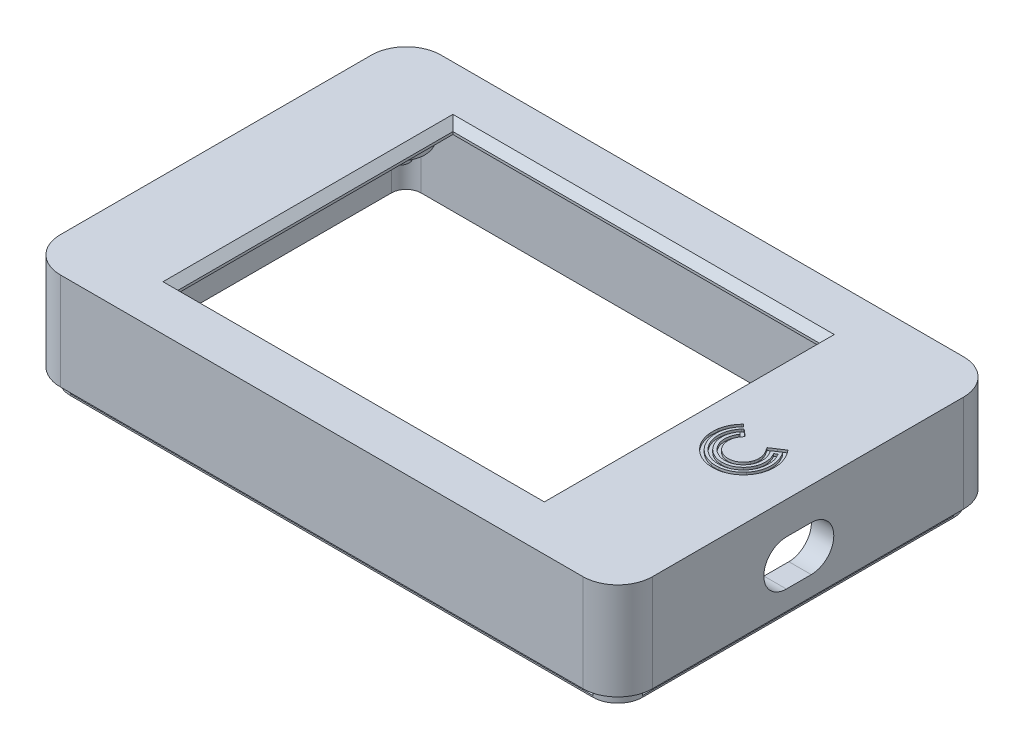
SolidWorks part; units mm, degrees
note: The reader was unsure of these and kept them because the rebuilt part matched: shared geometry of "Esquisse32<2>", "Esquisse48<2>".
other "Marquage2"
sketch "Esquisse44" plane through (-47.6, -20, 30.6) normal (-0.0394, -0.9945, 0.0967) x (-0.9946, 0.0483, 0.0914)
ref_plane "Front Plane" through (0, 0, 0) normal (0, 0, 1) x (1, 0, 0)
ref_plane "Top Plane" through (0, 0, 0) normal (0, 1, 0) x (1, 0, 0)
ref_plane "Right Plane" through (0, 0, 0) normal (1, 0, 0) x (0, 0, -1)
sketch "Esquisse1" plane through (0, 0, 0) normal (0, 1, 0) x (1, 0, 0)
  line L1 (-46, 29) -> (46, 29)
  line L2 (-46, 29) -> (-46, -29)
  line L3 (-46, -29) -> (46, -29)
  line L4 (46, 29) -> (46, -29)
  line L5 (-46, 29) -> (46, -29) construction
  line L6 (-46, -29) -> (46, 29) construction
  line L7 (-43, 25) -> (43, 25) construction
  line L8 (-43, 25) -> (-43, -25) construction
  line L9 (-31.6, -22.1) -> (27.3, -22.1)
  line L10 (-31.6, -22.1) -> (-31.6, 22.1)
  line L11 (-31.6, 22.1) -> (27.3, 22.1)
  line L12 (27.3, -22.1) -> (27.3, 22.1)
  line L13 (-31.6, -22.1) -> (27.3, 22.1) construction
  line L14 (-31.6, 22.1) -> (27.3, -22.1) construction
  line L15 (-43, -25) -> (43, -25) construction
  line L16 (43, 25) -> (43, -25) construction
  line L17 (-43, 25) -> (43, -25) construction
  line L18 (-43, -25) -> (43, 25) construction
  point P0 (0, 0)
  point P6 (0, 0)
  point P9 (-2.15, 0)
  dimension "D1" = 58
  dimension "D2" = 92
  dimension "D3" = 50
  dimension "D4" = 44.2
  dimension "D5" = 58.9
  dimension "D6" = 86
  dimension "D7" = 15.7
  dimension "D8" = 11.4
extrude "Boss.-Extru.1" add sketch "Esquisse1" along normal blind 1.6
fillet "Congé1" radius 4 4 edges at (46, 0.8, 29) (46, 0.8, -29) (-46, 0.8, 29) (-46, 0.8, -29)
chamfer "Chanfrein1" distance 1.2 angle 45 4 edges at (-2.15, 1.6, -22.1) (-31.6, 1.6, 0) (-2.15, 1.6, 22.1) (27.3, 1.6, 0)
sketch "Esquisse12" plane through (0, 0, 0) normal (0, -1, 0) x (1, 0, 0)
  line L0 (0, 0) -> (-39, 0) construction
  line L1 (-39, 21) -> (39, 21) construction
  line L2 (-39, 21) -> (-39, -21) construction
  line L3 (-39, -21) -> (39, -21) construction
  line L4 (39, 21) -> (39, -21) construction
  line L5 (-39, 21) -> (39, -21) construction
  line L6 (-39, -21) -> (39, 21) construction
  line L7 (-39, 0) -> (-45.8499, 0) construction
  circle A0 centre (-39, 21) radius 4
  circle A1 centre (-39, -21) radius 4
  circle A2 centre (39, 21) radius 4
  circle A3 centre (39, -21) radius 4
  point P0 (0, 0)
  dimension "D1" = 42
  dimension "D2" = 78
extrude "Boss.-Extru.2" add sketch "Esquisse12" along normal blind 4 contours A1 | A0 | A3 | A2
sketch "Esquisse13" plane through (0, 0, 0) normal (0, -1, 0) x (1, 0, 0)
  circle A1 centre (-39, 21) radius 1.45
  circle A2 centre (-39, -21) radius 1.45
  circle A3 centre (39, -21) radius 1.45
  circle A4 centre (39, 21) radius 1.45
extrude "Boss.-Extru.3" add sketch "Esquisse13" along normal blind 6.4
sketch "Esquisse32" plane through (0, 0, 0) normal (0, -1, 0) x (1, 0, 0)
  line L4 (46, -25) -> (46, 25)
  line L6 (46, -25) -> (46, 25)
  line L12 (42, 29) -> (-42, 29)
  line L14 (42, 29) -> (-42, 29)
  line L16 (-46, 25) -> (-46, -25)
  line L17 (-46, 25) -> (-46, -25)
  line L18 (-42, -29) -> (42, -29)
  line L19 (-42, -29) -> (42, -29)
  arc A4 (46, 25) -> (42, 29) centre (42, 25) ccw
  arc A6 (46, 25) -> (42, 29) centre (42, 25) ccw
  arc A12 (-42, 29) -> (-46, 25) centre (-42, 25) ccw
  arc A14 (-42, 29) -> (-46, 25) centre (-42, 25) ccw
  arc A16 (-46, -25) -> (-42, -29) centre (-42, -25) ccw
  arc A17 (-46, -25) -> (-42, -29) centre (-42, -25) ccw
  arc A18 (42, -29) -> (46, -25) centre (42, -25) ccw
  arc A19 (42, -29) -> (46, -25) centre (42, -25) ccw
  dimension "D1" = 0
extrude "Extru.-Mince3" add sketch "Esquisse32" along normal blind 16 thin thin type one direction reverse wall 1.6
extrude "Extru.-Mince4" add sketch "Esquisse32<2>" along normal blind 14 and the other way blind 1.6 thin
sketch "Esquisse32<2>" plane through (0, 0, 0) normal (0, -1, 0) x (1, 0, 0) same geometry as "Esquisse32"
sketch3d "Esquisse3D2"
  line L0 (-46, -14, -25) -> (-46, -16, -25) construction
  line L6 (-46, -15, -25) -> (-46, -15.75, -25)
  line L7 (-46, -15, -25) -> (-46, -14.25, -25)
  line L8 (-46, -14.25, -25) -> (-45.25, -15, -25)
  line L9 (-45.25, -15, -25) -> (-46, -15.75, -25)
extrude "Enlèv. mat.-Extru.3 ok" cut sketch "Esquisse3D2" along direction (0, 0, -1) on the side of the normal blind 50
sketch3d "Esquisse3D3"
  line L0 (46, -16, -25) -> (46, -14, -25) construction
  line L5 (46, -15, -25) -> (46, -15.75, -25)
  line L6 (46, -15, -25) -> (46, -14.25, -25)
  line L7 (46, -15.75, -25) -> (45.25, -15, -25)
  line L8 (45.25, -15, -25) -> (46, -14.25, -25)
extrude "Enlèv. mat.-Extru.4 ok" cut sketch "Esquisse3D3" along direction (0, 0, 1) on the side against the normal blind 50
sketch3d "Esquisse3D4"
  line L0 (42, -16, 29) -> (42, -14, 29) construction
  line L1 (42, -16, 27.4) -> (42, 0, 27.4) construction
  line L2 (42, -15, 29) -> (42, -14.25, 29)
  line L4 (42, -15, 29) -> (42, -14.25, 29)
  line L5 (42, -15, 29) -> (42, -15.75, 29)
  line L8 (42, -15.75, 29) -> (42, -15, 28.25)
  line L9 (42, -15, 28.25) -> (42, -14.25, 29)
extrude "Enlèv. mat.-Extru.5" cut sketch "Esquisse3D4" along direction (-1, 0, 0) on the side of the normal blind 84 contours L4 L5 L8 L9
sketch "Esquisse45" plane through (0, 1.6, 0) normal (0, 1, 0) x (1, 0, 0)
  line L2 (47.6, 0) -> (28.5, 0) construction
  line L3 (38.05, 0) -> (37.55, 0) construction
  line L4 (47.6, 25) -> (47.6, -25) construction
  line L6 (28.5, 23.3) -> (28.5, -23.3) construction
  point P0 (37.2387, 0)
  line B0 (34.2158, 2.7113) -> (34.3885, 2.9127)
  line B1 (34.3885, 2.9127) -> (34.4378, 2.8723)
  spline B2 degree 3 poles (32.2337, -0.3842) (32.2377, -0.4186) (32.2519, -0.5344) (32.264, -0.6416) knots 0 0 0 0 1 1 1 1
  spline B3 degree 3 poles (32.264, -0.6416) (32.3608, -1.4972) (32.7507, -2.4235) (33.303, -3.113) knots 1 1 1 1 2 2 2 2
  spline B4 degree 3 poles (33.303, -3.113) (33.4921, -3.3501) (33.8794, -3.7342) (34.1159, -3.9223) knots 2 2 2 2 3 3 3 3
  spline B5 degree 3 poles (34.1159, -3.9223) (34.8233, -4.4844) (35.7228, -4.8635) (36.5984, -4.9704) knots 3 3 3 3 4 4 4 4
  spline B6 degree 3 poles (36.5984, -4.9704) (36.9003, -5.0068) (37.7725, -4.9915) (38.0171, -4.946) knots 4 4 4 4 5 5 5 5
  spline B7 degree 3 poles (38.0171, -4.946) (38.532, -4.8532) (38.9035, -4.7337) (39.3593, -4.5183) knots 5 5 5 5 6 6 6 6
  spline B8 degree 3 poles (39.3593, -4.5183) (40.5052, -3.9735) (41.3817, -3.0412) (41.8615, -1.851) knots 6 6 6 6 7 7 7 7
  spline B9 degree 3 poles (41.8615, -1.851) (41.9771, -1.5647) (42.0958, -1.1348) (42.1539, -0.7967) knots 7 7 7 7 8 8 8 8
  spline B10 degree 3 poles (42.1539, -0.7967) (42.2119, -0.4607) (42.2156, 0.3707) (42.1644, 0.7032) knots 8 8 8 8 9 9 9 9
  spline B11 degree 3 poles (42.1644, 0.7032) (42.0391, 1.4819) (41.7529, 2.2231) (41.3225, 2.8733) knots 9 9 9 9 10 10 10 10
  spline B12 degree 3 poles (41.3225, 2.8733) (41.1105, 3.194) (40.8811, 3.4892) (40.8532, 3.4722) knots 10 10 10 10 11 11 11 11
  spline B13 degree 3 poles (40.8532, 3.4722) (40.8403, 3.4638) (40.3817, 3.1649) (39.835, 2.8066) knots 11 11 11 11 12 12 12 12
  spline B14 degree 3 poles (39.835, 2.8066) (39.5035, 2.5889) (39.1719, 2.3712) (38.8404, 2.1536) knots 12 12 12 12 13 13 13 13
  spline B15 degree 3 poles (38.8404, 2.1536) (38.9054, 2.0538) (38.9705, 1.9541) (39.0355, 1.8544) knots 13 13 13 13 14 14 14 14
  spline B16 degree 3 poles (39.0355, 1.8544) (39.381, 1.3248) (39.5374, 1.0087) (39.6375, 0.6245) knots 14 14 14 14 15 15 15 15
  spline B17 degree 3 poles (39.6375, 0.6245) (39.6876, 0.4377) (39.6916, 0.3863) (39.6888, -0.008) knots 15 15 15 15 16 16 16 16
  spline B18 degree 3 poles (39.6888, -0.008) (39.686, -0.4044) (39.6814, -0.4515) (39.6265, -0.6482) knots 16 16 16 16 17 17 17 17
  spline B19 degree 3 poles (39.6265, -0.6482) (39.5935, -0.7637) (39.5149, -0.9667) (39.4519, -1.097) knots 17 17 17 17 18 18 18 18
  spline B20 degree 3 poles (39.4519, -1.097) (38.7411, -2.5405) (36.904, -2.9519) (35.6554, -1.9446) knots 18 18 18 18 19 19 19 19
  spline B21 degree 3 poles (35.6554, -1.9446) (35.2612, -1.6269) (34.9623, -1.1748) (34.8242, -0.6895) knots 19 19 19 19 20 20 20 20
  spline B22 degree 3 poles (34.8242, -0.6895) (34.7448, -0.404) (34.7207, -0.1831) (34.7379, 0.1317) knots 20 20 20 20 21 21 21 21
  spline B23 degree 3 poles (34.7379, 0.1317) (34.7723, 0.7572) (34.9859, 1.2742) (35.407, 1.747) knots 21 21 21 21 22 22 22 22
  spline B24 degree 3 poles (35.407, 1.747) (35.5388, 1.8917) (35.5583, 1.9259) (35.5349, 1.9475) knots 22 22 22 22 23 23 23 23
  spline B25 degree 3 poles (35.5349, 1.9475) (35.5178, 1.9647) (35.275, 2.1679) (34.9938, 2.4034) knots 23 23 23 23 24 24 24 24
  spline B26 degree 3 poles (34.9938, 2.4034) (34.7126, 2.6389) (34.4634, 2.8485) (34.4378, 2.8723) knots 24 24 24 24 25 25 25 25
  spline B27 degree 3 poles (34.2158, 2.7113) (32.6545, 0.8902) (32.8979, -1.7703) (34.7563, -3.2073) knots 26 26 26 26 27 27 27 27
  spline B28 degree 3 poles (34.7563, -3.2073) (36.3328, -4.4248) (38.5491, -4.3067) (40.0012, -2.9264) knots 27 27 27 27 28 28 28 28
  spline B29 degree 3 poles (40.0012, -2.9264) (40.4497, -2.4988) (40.8092, -1.9419) (41.0188, -1.3519) knots 28 28 28 28 29 29 29 29
  spline B30 degree 3 poles (41.0188, -1.3519) (41.1937, -0.8539) (41.2521, -0.4579) (41.239, 0.1186) knots 29 29 29 29 30 30 30 30
  spline B31 degree 3 poles (41.239, 0.1186) (41.2292, 0.5623) (41.1819, 0.854) (41.056, 1.2448) knots 30 30 30 30 31 31 31 31
  spline B32 degree 3 poles (41.056, 1.2448) (40.9847, 1.4682) (40.687, 2.0981) (40.6463, 2.1112) knots 31 31 31 31 32 32 32 32
  spline B33 degree 3 poles (40.6463, 2.1112) (40.6292, 2.1177) (40.2679, 1.9015) (40.2119, 1.8525) knots 32 32 32 32 33 33 33 33
  spline B34 degree 3 poles (40.2119, 1.8525) (40.2075, 1.8483) (40.2561, 1.7451) (40.3216, 1.6225) knots 33 33 33 33 34 34 34 34
  spline B35 degree 3 poles (40.3216, 1.6225) (40.7763, 0.7558) (40.8507, -0.2454) (40.5271, -1.1667) knots 34 34 34 34 35 35 35 35
  spline B36 degree 3 poles (40.5271, -1.1667) (40.35, -1.669) (40.0748, -2.0977) (39.6735, -2.4956) knots 35 35 35 35 36 36 36 36
  spline B37 degree 3 poles (39.6735, -2.4956) (38.9507, -3.2105) (38.0762, -3.5515) (37.0737, -3.5081) knots 36 36 36 36 37 37 37 37
  spline B38 degree 3 poles (37.0737, -3.5081) (36.5274, -3.4849) (36.1168, -3.3771) (35.6406, -3.138) knots 37 37 37 37 38 38 38 38
  spline B39 degree 3 poles (35.6406, -3.138) (35.2904, -2.962) (35.0261, -2.7673) (34.7218, -2.4587) knots 38 38 38 38 39 39 39 39
  spline B40 degree 3 poles (34.7218, -2.4587) (34.0559, -1.7855) (33.7125, -0.941) (33.7192, 0.0125) knots 39 39 39 39 40 40 40 40
  spline B41 degree 3 poles (33.7192, 0.0125) (33.7229, 0.5374) (33.8181, 0.9696) (34.0337, 1.4609) knots 40 40 40 40 41 41 41 41
  spline B42 degree 3 poles (34.0337, 1.4609) (34.1186, 1.6532) (34.3181, 1.9946) (34.4089, 2.1054) knots 41 41 41 41 42 42 42 42
  spline B43 degree 3 poles (34.4089, 2.1054) (34.4262, 2.126) (34.4435, 2.1466) (34.4607, 2.1672) knots 42 42 42 42 43 43 43 43
  spline B44 degree 3 poles (34.4607, 2.1672) (34.5182, 2.1182) (34.5758, 2.0692) (34.6333, 2.0202) knots 43 43 43 43 44 44 44 44
  spline B45 degree 3 poles (34.6333, 2.0202) (34.7291, 1.9403) (34.8079, 1.8712) (34.8079, 1.8669) knots 44 44 44 44 45 45 45 45
  spline B46 degree 3 poles (34.8079, 1.8669) (34.8079, 1.8647) (34.7559, 1.7815) (34.6909, 1.6813) knots 45 45 45 45 46 46 46 46
  spline B47 degree 3 poles (34.6909, 1.6813) (34.2099, 0.9261) (34.0743, -0.0736) (34.3406, -0.9133) knots 46 46 46 46 47 47 47 47
  spline B48 degree 3 poles (34.3406, -0.9133) (34.5293, -1.5039) (34.9239, -2.0616) (35.4206, -2.4315) knots 47 47 47 47 48 48 48 48
  spline B49 degree 3 poles (35.4206, -2.4315) (35.6422, -2.5981) (36.0928, -2.8241) (36.3494, -2.8987) knots 48 48 48 48 49 49 49 49
  spline B50 degree 3 poles (36.3494, -2.8987) (36.6894, -2.9975) (36.912, -3.0269) (37.2914, -3.0167) knots 49 49 49 49 50 50 50 50
  spline B51 degree 3 poles (37.2914, -3.0167) (37.4821, -3.0117) (37.7051, -2.9918) (37.7952, -2.9731) knots 50 50 50 50 51 51 51 51
  spline B52 degree 3 poles (37.7952, -2.9731) (39.0034, -2.7181) (39.9053, -1.8244) (40.1731, -0.6157) knots 51 51 51 51 52 52 52 52
  spline B53 degree 3 poles (40.1731, -0.6157) (40.2351, -0.329) (40.2456, 0.2495) (40.1899, 0.552) knots 52 52 52 52 53 53 53 53
  spline B54 degree 3 poles (40.1899, 0.552) (40.1218, 0.9382) (39.9576, 1.3529) (39.6971, 1.7919) knots 53 53 53 53 54 54 54 54
  spline B55 degree 3 poles (39.6971, 1.7919) (39.6548, 1.8636) (39.6124, 1.9353) (39.5701, 2.007) knots 54 54 54 54 55 55 55 55
  spline B56 degree 3 poles (39.5701, 2.007) (39.7631, 2.1321) (39.9561, 2.2572) (40.1491, 2.3822) knots 55 55 55 55 56 56 56 56
  spline B57 degree 3 poles (40.1491, 2.3822) (40.4677, 2.59) (40.7389, 2.7595) (40.7496, 2.7594) knots 56 56 56 56 57 57 57 57
  spline B58 degree 3 poles (40.7496, 2.7594) (40.8053, 2.759) (41.1673, 2.1265) (41.3211, 1.759) knots 57 57 57 57 58 58 58 58
  spline B59 degree 3 poles (41.3211, 1.759) (41.9934, 0.1601) (41.724, -1.6015) (40.6048, -2.92) knots 58 58 58 58 59 59 59 59
  spline B60 degree 3 poles (40.6048, -2.92) (39.8853, -3.7699) (38.855, -4.3155) (37.7206, -4.4511) knots 59 59 59 59 60 60 60 60
  spline B61 degree 3 poles (37.7206, -4.4511) (37.3796, -4.4937) (36.8054, -4.479) (36.478, -4.421) knots 60 60 60 60 61 61 61 61
  spline B62 degree 3 poles (36.478, -4.421) (34.417, -4.0615) (32.8905, -2.3602) (32.7594, -0.2765) knots 61 61 61 61 62 62 62 62
  spline B63 degree 3 poles (32.7594, -0.2765) (32.6804, 0.984) (33.1131, 2.183) (33.9677, 3.0599) knots 62 62 62 62 63 63 63 63
  spline B64 degree 3 poles (33.9677, 3.0599) (34.0044, 3.0975) (34.0411, 3.1351) (34.0778, 3.1727) knots 63 63 63 63 64 64 64 64
  spline B65 degree 3 poles (34.0778, 3.1727) (34.0523, 3.1957) (34.0267, 3.2187) (34.0012, 3.2418) knots 64 64 64 64 65 65 65 65
  spline B66 degree 3 poles (34.0012, 3.2418) (33.9564, 3.2806) (33.867, 3.3584) (33.801, 3.4189) knots 65 65 65 65 66 66 66 66
  spline B67 degree 3 poles (33.801, 3.4189) (33.7598, 3.4549) (33.7186, 3.4909) (33.6775, 3.5269) knots 66 66 66 66 67 67 67 67
  spline B68 degree 3 poles (33.6775, 3.5269) (33.6321, 3.4772) (33.5868, 3.4275) (33.5414, 3.3778) knots 67 67 67 67 68 68 68 68
  spline B69 degree 3 poles (33.5414, 3.3778) (32.8635, 2.6476) (32.4439, 1.7913) (32.2827, 0.8025) knots 68 68 68 68 69 69 69 69
  spline B70 degree 3 poles (32.2827, 0.8025) (32.2491, 0.5927) (32.2133, -0.2341) (32.2337, -0.3842) knots 69 69 69 69 70 70 70 70
  line B71 (33.6775, 3.5269) -> (40.8532, 3.4722) construction
  line B72 (33.6775, 3.5269) -> (33.6242, -3.4722) construction
  line B73 (40.8532, 3.4722) -> (40.7999, -3.5269) construction
  line B74 (33.6242, -3.4722) -> (40.7999, -3.5269) construction
  line B75 (33.6775, 3.5269) -> (40.7999, -3.5269) construction
  line B76 (40.8532, 3.4722) -> (33.6242, -3.4722) construction
  dimension "D1" = 0.5
sketch_block_instance "Bloc2-1"
sketch_block "Bloc2"
sketch_block_instance "Bloc1-1"
sketch_block "Bloc1"
extrude "Enlèv. mat.-Extru.8" cut sketch "Esquisse45" against normal blind 0.4
sketch "Esquisse48" plane through (47.6, 0, 0) normal (1, 0, 0) x (0, 0, -1)
  line L0 (25, 1.6) -> (25, -14) construction
  line L1 (-25, 1.6) -> (25, 1.6) construction
  line L2 (-25, 1.6) -> (-25, -7.25) construction
  line L3 (-25, -7.25) -> (25, -7.25) construction
  line L4 (25, 1.6) -> (25, -7.25) construction
  line L5 (0, -7.25) -> (0, 1.6) construction
  line L6 (0.5, -7.25) -> (-3.5, -7.25) construction
  line L7 (0.5, -10.875) -> (-3.5, -10.875)
  line L8 (0.5, -3.625) -> (-3.5, -3.625)
  arc A0 (0.5, -10.875) -> (0.5, -3.625) centre (0.5, -7.25) ccw
  arc A1 (-3.5, -3.625) -> (-3.5, -10.875) centre (-3.5, -7.25) ccw
  point P11 (-1.5, -7.25)
  point P16 (-7.125, -7.25)
  point P17 (4.125, -7.25)
  dimension "D1" = 8.85
  dimension "D2" = 1.5
  dimension "D3" = 11.25
  dimension "D4" = 7.25
extrude "Extru.-Mince5" add sketch "Esquisse48" against normal blind 3.6 thin thin type one direction wall 1
extrude "Enlèv. mat.-Extru.11 ok" cut sketch "Esquisse48<2>" against normal blind 4
sketch "Esquisse48<2>" plane through (47.6, 0, 0) normal (1, 0, 0) x (0, 0, -1) same geometry as "Esquisse48"
sketch3d "Esquisse3D6"
  line L0 (-42, -16, -29) -> (-42, -14, -29) construction
  line L2 (-42, -15, -29) -> (-42, -15.75, -29)
  line L3 (-42, -15, -29) -> (-42, -14.25, -29)
  line L4 (-42, -16, -27.4) -> (-42, 0, -27.4) construction
  line L6 (-42, -15.75, -29) -> (-42, -15, -28.25)
  line L7 (-42, -15, -28.25) -> (-42, -14.25, -29)
extrude "Enlèv. mat.-Extru.15" cut sketch "Esquisse3D6" along direction (1, 0, 0) on the side against the normal blind 84 contours L7 L3 L2 L6
